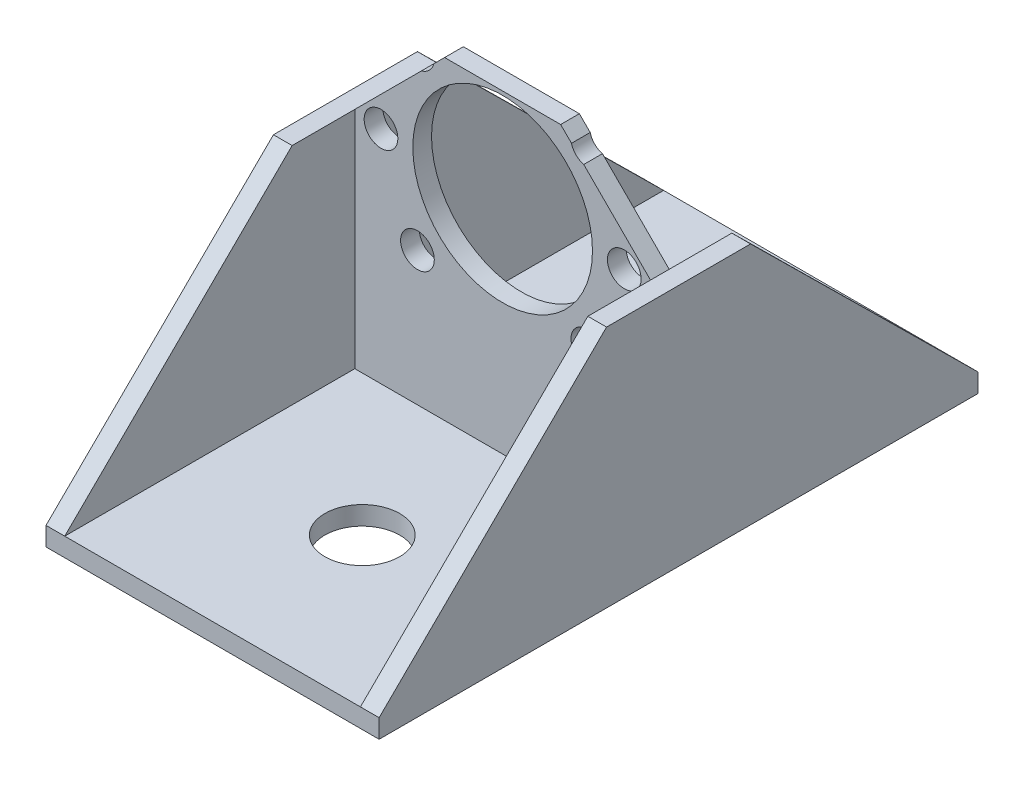
SolidWorks part; units mm, degrees
ref_plane "Alzado" through (0, 0, 0) normal (0, 0, 1) x (1, 0, 0)
ref_plane "Planta" through (0, 0, 0) normal (0, 1, 0) x (1, 0, 0)
ref_plane "Vista lateral" through (0, 0, 0) normal (1, 0, 0) x (0, 0, -1)
sketch "Croquis1" plane through (0, 0, 0) normal (0, 0, 1) x (1, 0, 0)
  line L0 (-19.75, 19.75) -> (19.75, 19.75)
  line L1 (-22.25, -22.25) -> (22.25, -22.25)
  line L2 (-22.25, -22.25) -> (-22.25, 22.25)
  line L3 (-22.25, 22.25) -> (22.25, 22.25)
  line L4 (22.25, -22.25) -> (22.25, 22.25)
  line L5 (-22.25, -22.25) -> (22.25, 22.25) construction
  line L6 (-22.25, 22.25) -> (22.25, -22.25) construction
  line L7 (19.75, -19.75) -> (19.75, 19.75)
  line L8 (-19.75, -19.75) -> (19.75, -19.75)
  line L9 (-19.75, -19.75) -> (-19.75, 19.75)
  point P0 (0, 0)
  dimension "D1" = 44.5
  dimension "D2" = 44.5
  dimension "D3" = 2.5
extrude "Saliente-Extruir1" add sketch "Croquis1" along normal blind 40 and the other way blind 40
sketch "Croquis2" plane through (22.25, 0, 0) normal (1, 0, 0) x (0, 0, -1)
  line L0 (0, 19.75) -> (-40, -19.75)
  line L1 (0, 19.75) -> (40, -19.75)
  line L2 (40, 22.25) -> (-40, 22.25)
  line L3 (-40, 22.25) -> (-40, -19.75)
  line L4 (40, 19.75) -> (-40, 19.75)
  line L5 (-40, 19.75) -> (-40, -19.75)
  line L6 (-40, -19.75) -> (40, -19.75)
  line L7 (40, -19.75) -> (40, 19.75)
  line L8 (40, 19.75) -> (-40, 19.75) construction
  line L9 (-40, 19.75) -> (-40, -19.75)
  line L10 (-40, -19.75) -> (40, -19.75)
  line L11 (40, -19.75) -> (40, 19.75)
  line L12 (40, 22.25) -> (40, -19.75)
  line L13 (-9.6203, 10.25) -> (9.6203, 10.25)
  line M6 (40, 22.25) -> (-40, 22.25)
  line M7 (-40, 22.25) -> (-40, -22.25)
  line M9 (40, -22.25) -> (40, 22.25)
  dimension "D2" = 30
  dimension "D1" = 0
extrude "Cortar-Extruir1" cut sketch "Croquis2" against normal up to surface (44.5 mm away) contours L0 L8 L3 | L8 L1 M9 | L8 M9 M6 M7 | L0 L13 L1 region at (22.25, 13.4167, 0) region at (22.25, 6.5833, -26.6667) region at (22.25, 21, 0) region at (22.25, 6.5833, 26.6667) up to face at (-22.25, 0, 0)
sketch "Croquis3" plane through (0, 0, 0) normal (0, 0, 1) x (1, 0, 0)
  line L0 (19.75, 10.25) -> (19.75, -19.75) construction
  line L1 (-19.75, -19.75) -> (19.75, -19.75) construction
  line L2 (-19.75, -19.75) -> (-19.75, 10.25) construction
  line L3 (19.75, 10.25) -> (19.75, -19.75)
  line L4 (-19.75, -19.75) -> (19.75, -19.75)
  line L5 (-19.75, -19.75) -> (-19.75, 10.25)
  line L6 (19.75, 10.25) -> (-19.75, 10.25)
  line L7 (0, 0) -> (0, 22.25) construction
  line L8 (-7.75, 22.25) -> (7.75, 22.25)
  line L9 (7.75, 22.25) -> (19.75, 10.25)
  line L10 (-7.75, 22.25) -> (-19.75, 10.25)
  dimension "D1" = 12
  dimension "D2" = 45
extrude "Saliente-Extruir2" add sketch "Croquis3" along normal blind 1.25 and the other way blind 1.25 contours L3 L6 L5 L4 | L6 L7 L8 L10 | L7 L6 L9 L8 region at (0, -4.75, 0) region at (7.3114, 15.3773, 0) region at (-7.3114, 15.3773, 0)
sketch "Croquis4" plane through (0, -22.25, 0) normal (0, -1, 0) x (1, 0, 0)
  line L0 (0, 20) -> (0, -20) construction
  circle A0 centre (0, -20) radius 5
  circle A1 centre (0, 20) radius 5
  point P4 (0, 0)
  dimension "D2" = 10
  dimension "D1" = 40
extrude "Cortar-Extruir2" cut sketch "Croquis4" against normal up to surface (2.5 mm away) up to face at (0, -19.75, -20.625)
sketch "Croquis7" plane through (0, 0, 1.25) normal (0, 0, 1) x (1, 0, 0)
  circle A0 centre (0, 9.75) radius 12 construction
  circle A1 centre (0, 9.75) radius 12
extrude "Cortar-Extruir5" cut sketch "Croquis7" against normal up to surface (2.5 mm away) up to face at (0, 4.25, -1.25)
sketch "Croquis8" plane through (0, 0, 1.25) normal (0, 0, 1) x (1, 0, 0)
  line L0 (16.25, 9.75) -> (-16.25, 9.75) construction
  circle A0 centre (-11.3799, 21.35) radius 2.25 construction
  circle A1 centre (11.3799, 21.35) radius 2.25 construction
  circle A2 centre (-11.3799, 21.35) radius 2.25
  circle A3 centre (11.3799, 21.35) radius 2.25
  circle A4 centre (-16.25, 9.75) radius 2.25 construction
  circle A5 centre (-16.25, 9.75) radius 2.25
  circle A6 centre (16.25, 9.75) radius 2.25 construction
  circle A7 centre (16.25, 9.75) radius 2.25
  circle A8 centre (-11.3799, -1.85) radius 2.25
  circle A9 centre (11.3799, -1.85) radius 2.25
extrude "Cortar-Extruir6" cut sketch "Croquis8" against normal up to surface (2.5 mm away) up to face at (12, 9.75, -1.25)
equation "\"D2@Croquis1\"=\"D1@Croquis1\""
